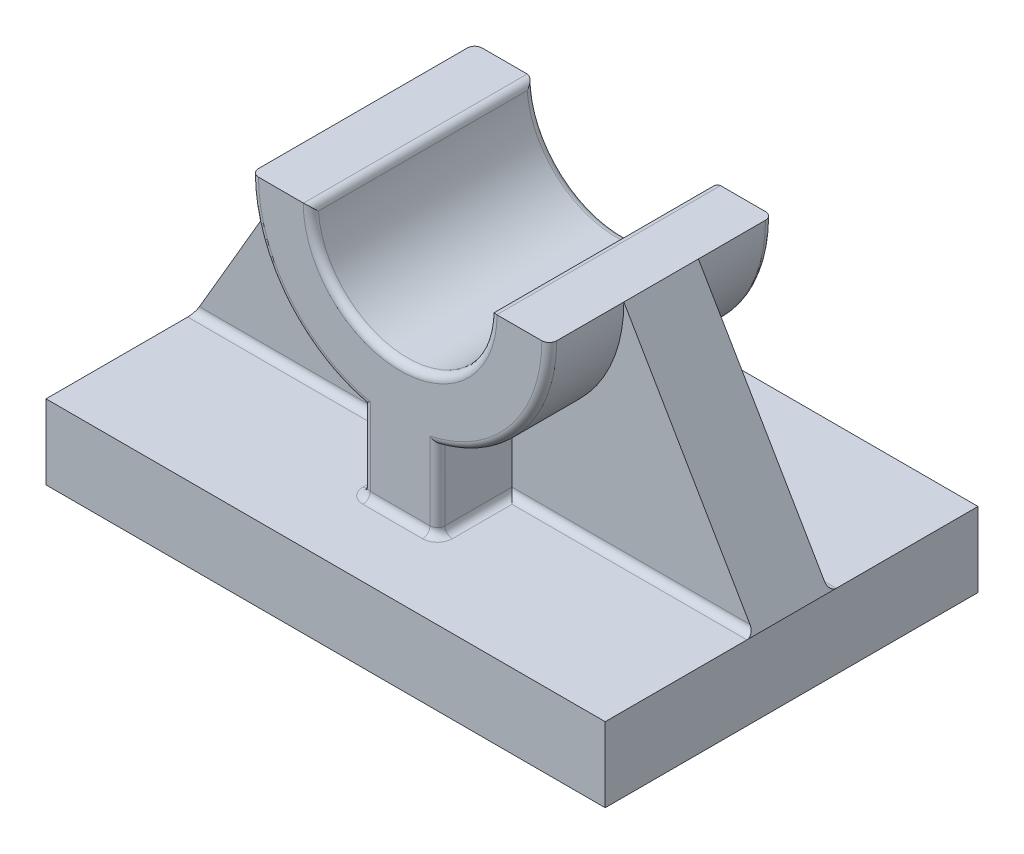
SolidWorks part; units mm, degrees
ref_plane "Front Plane" through (0, 0, 0) normal (0, 0, 1) x (1, 0, 0)
ref_plane "Top Plane" through (0, 0, 0) normal (0, 1, 0) x (1, 0, 0)
ref_plane "Right Plane" through (0, 0, 0) normal (1, 0, 0) x (0, 0, -1)
sketch "Sketch1" plane through (0, 0, 0) normal (0, 0, 1) x (1, 0, 0)
  line L1 (-37.5, 0) -> (37.5, 0)
  line L2 (37.5, 0) -> (37.5, 10)
  line L3 (37.5, 10) -> (-37.5, 10)
  line L4 (-37.5, 0) -> (-37.5, 10)
  line L5 (-5, 20.6351) -> (-5, 10)
  line L6 (5, 20.6351) -> (5, 10)
  line L7 (-20, 40) -> (-12, 40)
  line L8 (12, 40) -> (20, 40)
  line L9 (20, 40) -> (37.5, 10)
  line L10 (-20, 40) -> (-37.5, 10)
  arc A0 (-12, 40) -> (12, 40) centre (0, 40) ccw
  arc A1 (5, 20.6351) -> (20, 40) centre (0, 40) ccw
  arc A2 (-20, 40) -> (-5, 20.6351) centre (0, 40) ccw
  point P8 (0, 0)
  point P9 (0, 10)
  dimension "D1" = 24
  dimension "D2" = 40
  dimension "D8" = 8
  dimension "D3" = 40
  dimension "D4" = 0
  dimension "D5" = 10
  dimension "D6" = 10
  dimension "D7" = 75
  dimension "D9" = 30
  dimension "D10" = 10.6351
  dimension "D11" = 30
  dimension "D12" = 10
extrude "Boss-Extrude5" add sketch "Sketch1" along normal mid plane 50 contours L4 L1 L2 L3 region at (0, 5, 0)
extrude "Boss-Extrude6" add sketch "Sketch1<9>" along normal mid plane 30 contours L7 A2 L5 L3 L6 A1 L8 A0 region at (0, 26.6667, 0)
sketch "Sketch1<9>" plane through (0, 0, 0) normal (0, 0, 1) x (1, 0, 0) same geometry as "Sketch1"
extrude "Boss-Extrude7" add sketch "Sketch1<10>" along normal mid plane 10 contours A1 L6 L3 L9 | A2 L10 L3 L5 region at (-20.0801, 19.2626, 0) region at (20.0801, 19.2626, 0)
sketch "Sketch1<10>" plane through (0, 0, 0) normal (0, 0, 1) x (1, 0, 0) same geometry as "Sketch1"
fillet "Fillet2" radius 1 12 edges at (12, 40, 0) (0, 28, 15) (-12, 40, 0) (0, 28, -15) (-15.8114, 27.7526, 15) (-5, 15.3175, 15) (5, 15.3175, 15) (15.8114, 27.7526, 15) (5, 15.3175, -15) (15.8114, 27.7526, -15) (-5, 15.3175, -15) (-15.8114, 27.7526, -15)
fillet "Fillet3" radius 1 14 edges at (-5, 10, 9.5) (-4.7071, 10, 14.7071) (0, 10, 15) (4.7071, 10, 14.7071) (-5, 10, -9.5) (-4.7071, 10, -14.7071) (0, 10, -15) (4.7071, 10, -14.7071) (-21.25, 10, 5) (5, 10, 9.5) (5, 10, -9.5) (-21.25, 10, -5) (21.25, 10, -5) (21.25, 10, 5)
